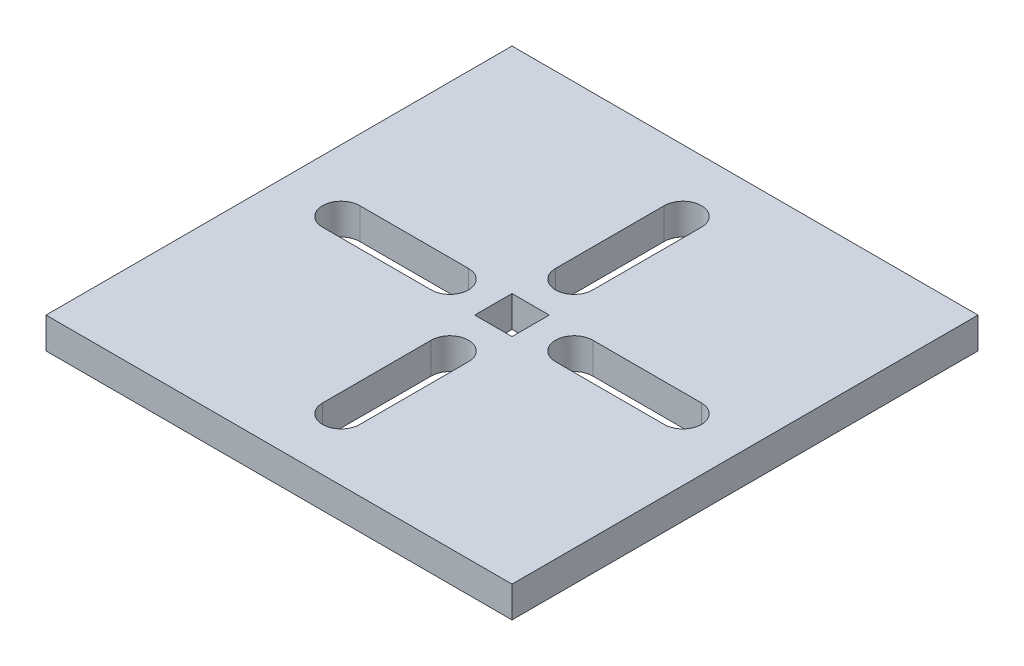
SolidWorks part; units mm, degrees
ref_plane "前基準面" through (0, 0, 0) normal (0, 0, 1) x (1, 0, 0)
ref_plane "上基準面" through (0, 0, 0) normal (0, 1, 0) x (1, 0, 0)
ref_plane "右基準面" through (0, 0, 0) normal (1, 0, 0) x (0, 0, -1)
sketch "Sketch1" plane through (0, 0, 0) normal (0, 1, 0) x (1, 0, 0)
  line L1 (-75, 75) -> (75, 75)
  line L2 (-75, 75) -> (-75, -75)
  line L3 (-75, -75) -> (75, -75)
  line L4 (75, 75) -> (75, -75)
  line L5 (-75, 75) -> (75, -75) construction
  line L6 (-75, -75) -> (75, 75) construction
  point P0 (0, 0)
  dimension "D1" = 150
extrude "Boss-Extrude1" add sketch "Sketch1" along normal blind 10
sketch "Sketch3" plane through (0, 10, 0) normal (0, 1, 0) x (1, 0, 0)
  line L1 (-6, 6) -> (6, 6)
  line L2 (-6, 6) -> (-6, -6)
  line L3 (-6, -6) -> (6, -6)
  line L4 (6, 6) -> (6, -6)
  line L5 (-6, 6) -> (6, -6) construction
  line L6 (-6, -6) -> (6, 6) construction
  point P0 (0, 0)
  dimension "D1" = 12
extrude "Cut-Extrude2" cut sketch "Sketch3" against normal through all
sketch "Sketch2" plane through (0, 10, 0) normal (0, 1, 0) x (1, 0, 0)
  line L0 (0, 0) -> (20, 0) construction
  line L1 (20, 0) -> (55, 0) construction
  line L2 (20, 6) -> (55, 6)
  line L3 (20, -6) -> (55, -6)
  arc A0 (20, 6) -> (20, -6) centre (20, 0) ccw
  arc A1 (55, -6) -> (55, 6) centre (55, 0) ccw
  point P3 (37.5, 0)
  dimension "D2" = 6
  dimension "D1" = 35
  dimension "D3" = 20
extrude "Cut-Extrude1" cut sketch "Sketch2" against normal through all
ref_axis "基準軸1" through (0, 10.5, 0) along (0, -1, 0)
pattern_circular "環狀複製排列1" count 4 over 360 about axis through (0, 10.5, 0) along (0, -1, 0) of "Cut-Extrude1"
